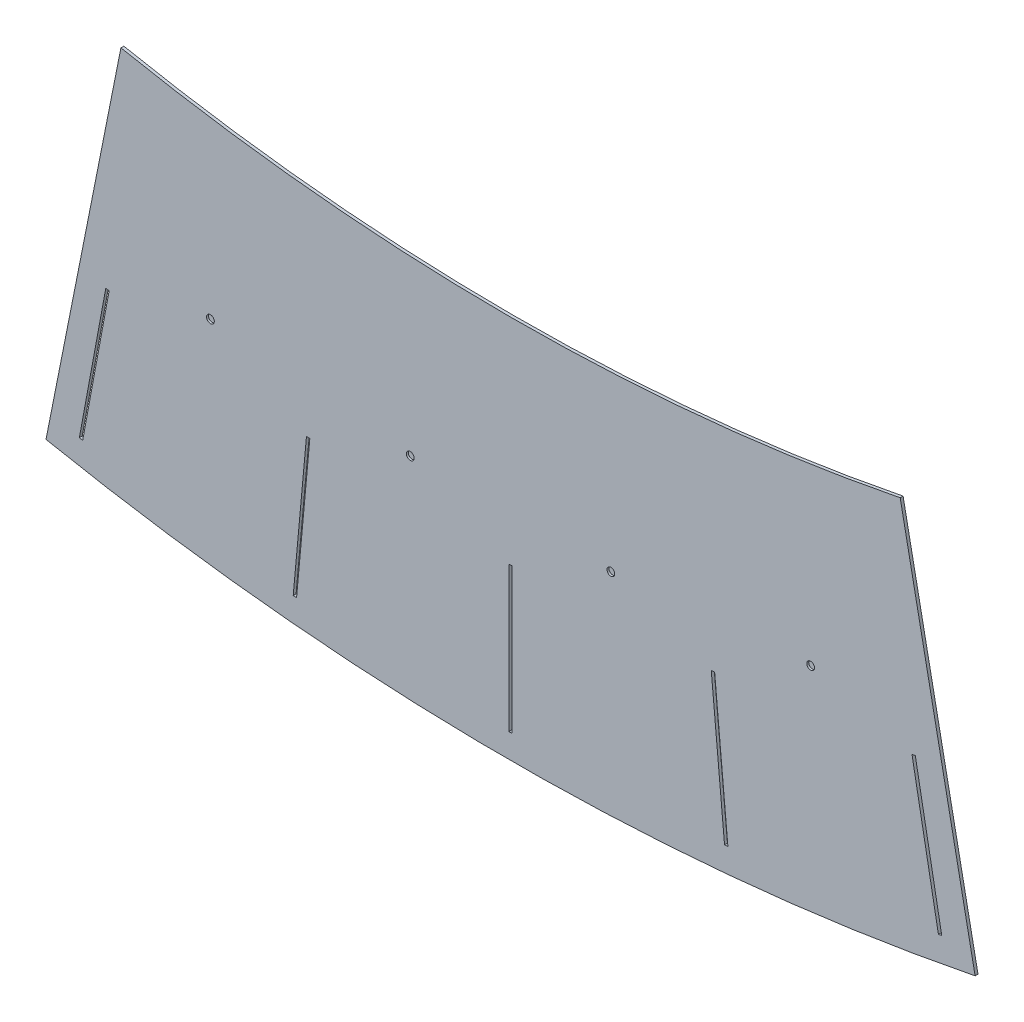
SolidWorks part; units mm, degrees
ref_plane "Front Plane" through (0, 0, 0) normal (0, 0, 1) x (1, 0, 0)
ref_plane "Top Plane" through (0, 0, 0) normal (0, 1, 0) x (1, 0, 0)
ref_plane "Right Plane" through (0, 0, 0) normal (1, 0, 0) x (0, 0, -1)
sketch "Sketch1" plane through (0, 0, 0) normal (0, 0, 1) x (1, 0, 0)
  line L0 (0, 0) -> (0, -43.1477) construction
  line L1 (0, 0) -> (-480.3124, -2414.6934) construction
  line L2 (0, 0) -> (480.3124, -2414.6934) construction
  line L3 (-480.3124, -2414.6934) -> (-402.8615, -2025.3216)
  line L4 (480.3124, -2414.6934) -> (402.8615, -2025.3216)
  line L5 (0, -2065) -> (0, -2462) construction
  line L6 (-207.5215, -2277.566) -> (-221.2468, -2426.9367)
  line L7 (-1.75, -2287) -> (1.75, -2287)
  line L8 (-1.75, -2287) -> (-1.75, -2437)
  line L9 (-1.75, -2437) -> (1.75, -2437)
  line L10 (1.75, -2287) -> (1.75, -2437)
  line L11 (-224.7321, -2426.6165) -> (-221.2468, -2426.9367)
  line L12 (-211.0069, -2277.2457) -> (-224.7321, -2426.6165)
  line L13 (-211.0069, -2277.2457) -> (-207.5215, -2277.566)
  line L14 (-415.052, -2249.0229) -> (-442.3873, -2396.5111)
  line L15 (-445.8287, -2395.8733) -> (-442.3873, -2396.5111)
  line L16 (-418.4933, -2248.3851) -> (-445.8287, -2395.8733)
  line L17 (-418.4933, -2248.3851) -> (-415.052, -2249.0229)
  line L18 (211.0069, -2277.2457) -> (224.7321, -2426.6165)
  line L19 (221.2468, -2426.9367) -> (224.7321, -2426.6165)
  line L20 (207.5215, -2277.566) -> (221.2468, -2426.9367)
  line L21 (207.5215, -2277.566) -> (211.0069, -2277.2457)
  line L22 (418.4933, -2248.3851) -> (445.8287, -2395.8733)
  line L23 (442.3873, -2396.5111) -> (445.8287, -2395.8733)
  line L24 (415.052, -2249.0229) -> (442.3873, -2396.5111)
  line L25 (415.052, -2249.0229) -> (418.4933, -2248.3851)
  arc A0 (-480.3124, -2414.6934) -> (480.3124, -2414.6934) centre (0, 0) ccw
  arc A1 (-402.8615, -2025.3216) -> (402.8615, -2025.3216) centre (0, 0) ccw
  point P15 (0, -2287)
  point P16 (1.75, -2362)
  point P27 (0, 0)
  point P37 (0, 0)
  dimension "D3" = 397
  dimension "D1" = 22.5
  dimension "D2" = 2462
  dimension "D4" = 3.5
  dimension "D5" = 100
  dimension "D6" = 150
  dimension "D7" = 3
  dimension "D8" = 3
extrude "Boss-Extrude1" add sketch "Sketch1" along normal blind 3
ref_axis "Axis1" through (0, 0, 3) along (0, 0, -1)
sketch "Sketch3" plane through (0, 0, 3) normal (0, 0, 1) x (1, 0, 0)
  line L0 (0, 0) -> (340.5165, -2438.3381) construction
  line L1 (0, 0) -> (480.3124, -2414.6934) construction
  arc A11 (-480.3124, -2414.6934) -> (480.3124, -2414.6934) centre (0, 0) ccw construction
  circle A12 centre (310.3046, -2222) radius 4
  circle A13 centre (103.7305, -2241.1633) radius 4
  circle A14 centre (-103.7305, -2241.1633) radius 4
  circle A15 centre (-310.3046, -2222) radius 4
  point P18 (0, 0)
  dimension "D1" = 3.3
  dimension "D2" = 8
  dimension "D3" = 240
extrude "Cut-Extrude1" cut sketch "Sketch3" against normal blind 2
